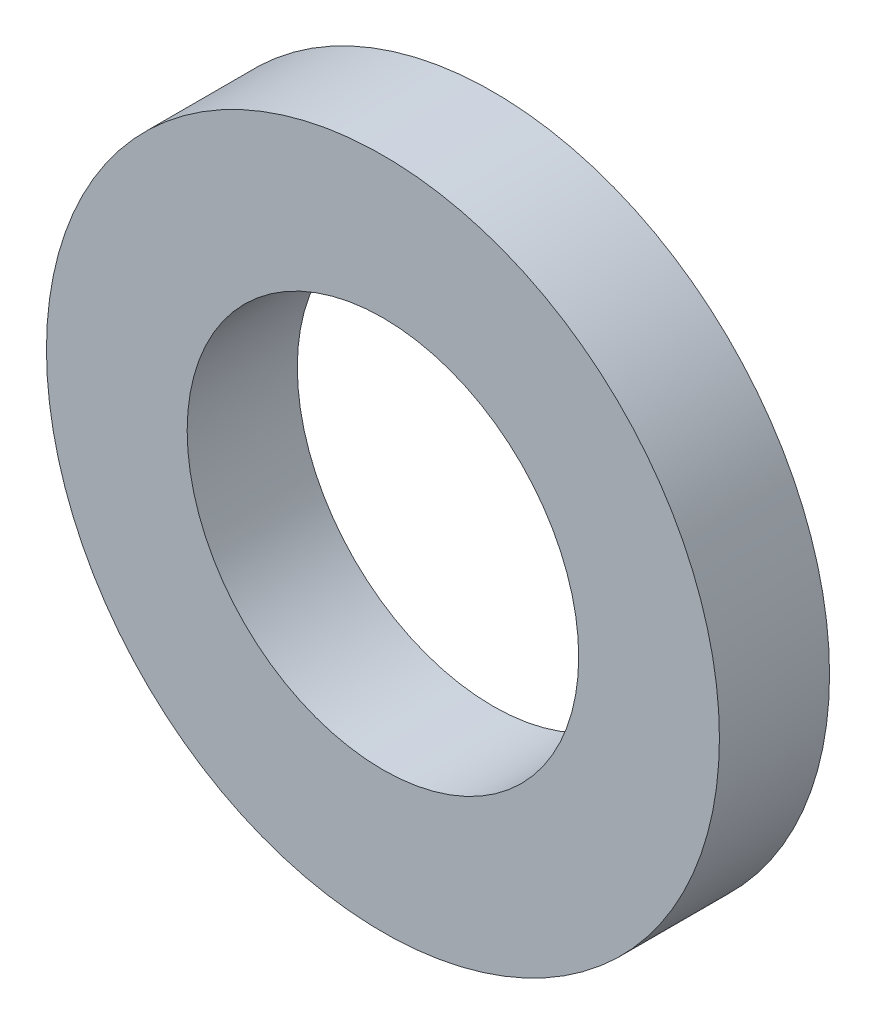
SolidWorks part; units mm, degrees
material "Alloy Steel"
ref_plane "Front Plane" through (0, 0, 0) normal (0, 0, 1) x (1, 0, 0)
ref_plane "Top Plane" through (0, 0, 0) normal (0, 1, 0) x (1, 0, 0)
ref_plane "Right Plane" through (0, 0, 0) normal (1, 0, 0) x (0, 0, -1)
sketch "Sketch1" plane through (0, 0, 0) normal (0, 0, 1) x (1, 0, 0)
  circle A0 centre (0, 0) radius 5.5
  circle A1 centre (0, 0) radius 3.2
  dimension "OD" = 11
  dimension "ID1" = 6.4
extrude "Boss-Extrude1" add sketch "Sketch1" along normal blind 1.8
ref_axis "Center Axis 1" [suppressed] through (0, 0, 1.8) along (0, 0, -1)
ref_plane "Contact Plane 1" [suppressed] through (0, 0, 1.8) normal (0, 0, 1) x (1, 0, 0)
ref_plane "Contact Plane 2" [suppressed] through (0, 0, 0) normal (0, 0, -1) x (-1, 0, 0)
